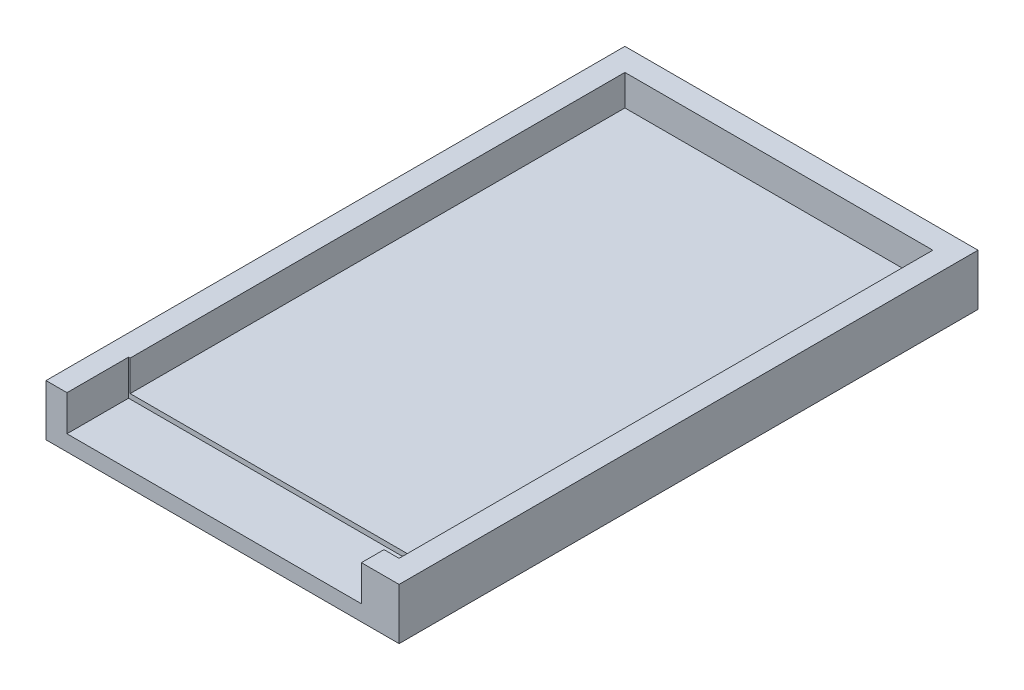
SolidWorks part; units mm, degrees
ref_plane "Front Plane" through (0, 0, 0) normal (0, 0, 1) x (1, 0, 0)
ref_plane "Top Plane" through (0, 0, 0) normal (0, 1, 0) x (1, 0, 0)
ref_plane "Right Plane" through (0, 0, 0) normal (1, 0, 0) x (0, 0, -1)
sketch "Sketch2" plane through (0, 0, 0) normal (0, 1, 0) x (1, 0, 0)
  line L0 (-17.2, 28.2) -> (-17.2, -28.2)
  line L1 (-15, 26) -> (15, 26)
  line L2 (-15, 26) -> (-15, -26)
  line L3 (-15, -26) -> (15, -26)
  line L4 (15, 26) -> (15, -26)
  line L5 (-17.2, -28.2) -> (17.2, -28.2)
  line L6 (17.2, 28.2) -> (17.2, -28.2)
  line L7 (-17.2, 28.2) -> (17.2, 28.2)
  point P4 (0, 26)
  point P10 (-15, 0)
  dimension "D1" = 52
  dimension "D2" = 30
  dimension "D3" = 2.2
extrude "Boss-Extrude1" add sketch "Sketch2" along normal blind 2 contours L2 L1 L4 L3
extrude "Boss-Extrude2" add sketch "Sketch2<3>" along normal blind 5
sketch "Sketch2<3>" plane through (0, 0, 0) normal (0, 1, 0) x (1, 0, 0) same geometry as "Sketch2"
sketch "Sketch3" plane through (0, 0, 28.2) normal (0, 0, 1) x (1, 0, 0)
  line L1 (13.5295, 5.9072) -> (-15.1562, 5.9072)
  line L2 (13.5295, 5.9072) -> (13.5295, 1.5323)
  line L3 (13.5295, 1.5323) -> (-15.1562, 1.5323)
  line L4 (-15.1562, 5.9072) -> (-15.1562, 1.5323)
extrude "Cut-Extrude1" cut sketch "Sketch3" against normal blind 6
